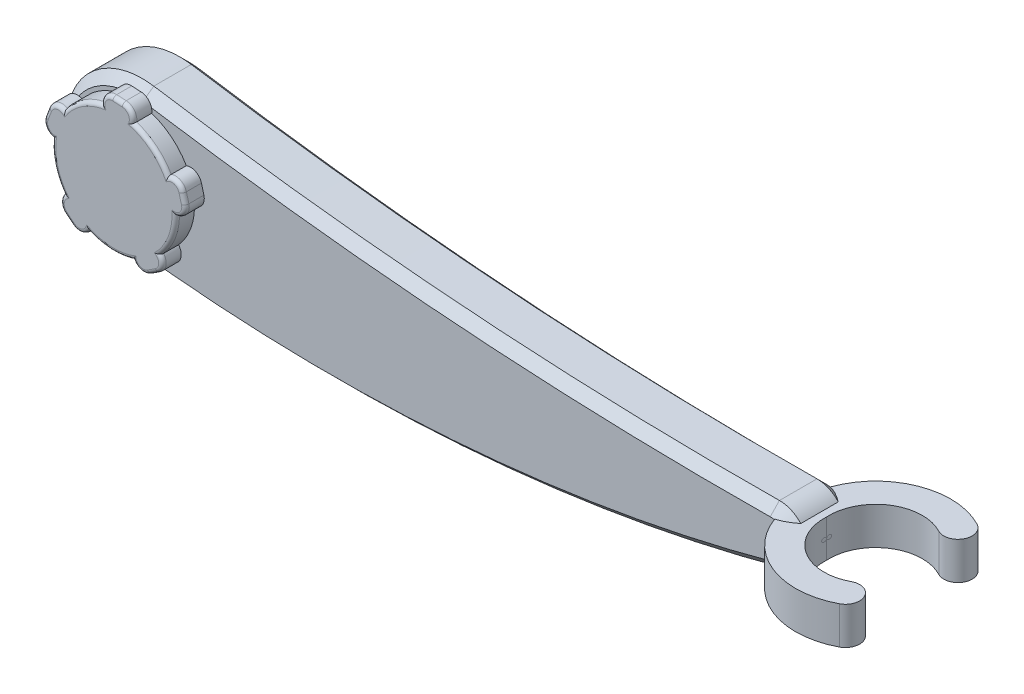
SolidWorks part; units mm, degrees
ref_plane "Front Plane" through (0, 0, 0) normal (0, 0, 1) x (1, 0, 0)
ref_plane "Top Plane" through (0, 0, 0) normal (0, 1, 0) x (1, 0, 0)
ref_plane "Right Plane" through (0, 0, 0) normal (1, 0, 0) x (0, 0, -1)
sketch "Sketch1" plane through (0, 0, 0) normal (0, 0, 1) x (1, 0, 0)
  line L0 (-61.6804, 0) -> (108.3196, 0) construction
  circle A0 centre (-61.6804, 0) radius 20
  circle A1 centre (108.3196, 0) radius 7.5
  arc A2 (-58.5521, 19.7538) -> (108.2417, 7.4996) centre (97.86, 1007.4457) ccw
  arc A3 (-64.1419, -19.8479) -> (110.304, -7.2327) centre (-8.7576, 426.7308) ccw
  dimension "D2" = 15
  dimension "D3" = 40
  dimension "D4" = 1000
  dimension "D5" = 450
  dimension "D1" = 170
extrude "Boss-Extrude1" add sketch "Sketch1" along normal mid plane 15 contours L0 A0 A3 A1 | A1 | A0 | A0 L0 A1 A2 region at (16.8751, 6.0296, 0) region at (-48.8117, -14.5633, 0) region at (20.2083, -10.4688, 0) region at (103.1396, 5.1265, 0)
chamfer "Chamfer1" distance 2.5 angle 45 8 edges at (-81.4841, 2.7953, -7.5) (23.6998, -22.0971, -7.5) (115.7472, 1.0397, -7.5) (24.5882, 10.1337, -7.5) (115.7472, 1.0397, 7.5) (23.6998, -22.0971, 7.5) (-81.4841, 2.7953, 7.5) (24.5882, 10.1337, 7.5)
sketch "Sketch2" plane through (0, 0, 7.5) normal (0, 0, 1) x (1, 0, 0)
  circle A0 centre (-61.6804, 0) radius 16.5
  dimension "D1" = 33
extrude "Boss-Extrude2" add sketch "Sketch2" along normal blind 5
sketch "Sketch3" plane through (0, 0, 12.5) normal (0, 0, 1) x (1, 0, 0)
  line L0 (-61.6804, 0) -> (-45.5901, 0)
  line L1 (-42.6923, 3.7765) -> (-43.348, 6.2235)
  line L2 (-47.7458, 8.0452) -> (-61.6804, 0)
  line L3 (-61.6804, 0) -> (-43.0201, 5) construction
  line L4 (-49.723, -10.7665) -> (-61.6804, 0)
  line L5 (-61.6804, 0) -> (-56.7082, -15.3028)
  line L6 (-52.2211, -16.8918) -> (-50.0964, -15.512)
  line L7 (-68.2249, -14.6992) -> (-61.6804, 0)
  line L8 (-61.6804, 0) -> (-74.6977, -9.4577)
  line L9 (-74.8223, -14.2161) -> (-72.8535, -15.8105)
  line L10 (-77.6826, 1.6819) -> (-61.6804, 0)
  line L11 (-61.6804, 0) -> (-74.6977, 9.4577)
  line L12 (-79.2618, 8.1057) -> (-80.1697, 5.7406)
  line L13 (-65.0258, 15.7387) -> (-61.6804, 0)
  line L14 (-61.6804, 0) -> (-56.7082, 15.3028)
  line L15 (-59.4044, 19.2257) -> (-61.9343, 19.3583)
  arc A0 (-42.6923, 3.7765) -> (-45.5901, 0) centre (-45.5901, 3) cw
  circle A1 centre (-61.6804, 0) radius 16.5
  circle A2 centre (-61.6804, 0) radius 16.5
  arc A3 (-43.348, 6.2235) -> (-47.7458, 8.0452) centre (-46.2458, 5.4471) ccw
  arc A4 (-50.0964, -15.512) -> (-49.723, -10.7665) centre (-51.7303, -12.996) ccw
  arc A5 (-52.2211, -16.8918) -> (-56.7082, -15.3028) centre (-53.855, -14.3758) cw
  arc A6 (-72.8535, -15.8105) -> (-68.2249, -14.6992) centre (-70.9656, -13.479) ccw
  arc A7 (-74.8223, -14.2161) -> (-74.6977, -9.4577) centre (-72.9344, -11.8847) cw
  arc A8 (-80.1697, 5.7406) -> (-77.6826, 1.6819) centre (-77.369, 4.6655) ccw
  arc A9 (-79.2618, 8.1057) -> (-74.6977, 9.4577) centre (-76.4611, 7.0306) cw
  arc A10 (-61.9343, 19.3583) -> (-65.0258, 15.7387) centre (-62.0913, 16.3624) ccw
  arc A11 (-59.4044, 19.2257) -> (-56.7082, 15.3028) centre (-59.5614, 16.2299) cw
  circle A12 centre (-61.6804, 0) radius 2
  point P9 (-41.6804, 0)
  point P39 (-61.6804, 0)
  circle M28 centre (-61.6804, 0) radius 16.5
  dimension "D4" = 3
  dimension "D6" = 4
  dimension "D2" = 30
  dimension "D3" = 20
  dimension "D1" = 0
  dimension "D5" = 5
extrude "Boss-Extrude3" add sketch "Sketch3" against normal blind 5 contours A11 L15 A10 M28 | A2 L3 L1 A3 | L3 A0 L1 M28 | A5 L6 A4 M28 | A7 L9 A6 M28 | A9 L12 A8 M28 region at (-45.1235, 6.4563, 12.5) region at (-44.1136, 2.6871, 12.5) region at (-52.06, -14.8141, 12.5) region at (-72.7965, -13.7273, 12.5) region at (-78.1709, 6.3301, 12.5) region at (-60.7559, 17.6395, 12.5)
fillet "Fillet1" radius 1 20 edges at (-64.2338, 18.4623, 12.5) (-60.6693, 19.292, 12.5) (-57.2111, 18.0943, 12.5) (-51.2966, 12.8229, 12.5) (-44.9107, 8.1337, 12.5) (-43.0201, 5, 12.5) (-43.0906, 1.3409, 12.5) (-46.2763, -5.9131, 12.5) (-48.7627, -13.4355, 12.5) (-51.1588, -16.2019, 12.5) (-54.6606, -17.2656, 12.5) (-62.5439, -16.4774, 12.5) (-70.4665, -16.4372, 12.5) (-73.8379, -15.0133, 12.5) (-75.9317, -12.0116, 12.5) (-77.6182, -4.2705, 12.5) (-80.0282, 3.2767, 12.5) (-79.7158, 6.9231, 12.5) (-77.508, 9.842, 12.5) (-70.6669, 13.8381, 12.5)
sketch "Sketch4" plane through (0, 0, 7.5) normal (0, 0, 1) x (1, 0, 0)
  circle A1 centre (108.3196, 0) radius 5
  dimension "D1" = 10
extrude "Cut-Extrude1" [suppressed] cut sketch "Sketch4" against normal blind 10
sketch "Sketch7" plane through (0, 0, -7.5) normal (0, 0, -1) x (-1, 0, 0)
  circle A0 centre (61.6804, 0) radius 5
  dimension "D1" = 10
extrude "Boss-Extrude4" add sketch "Sketch7" along normal blind 10
sketch "Sketch8" plane through (0, 0, 0) normal (0, 1, 0) x (1, 0, 0)
  line L0 (0, 0) -> (167.1151, 0) construction
  line L1 (108.2417, -5) -> (108.2417, 5) construction
  line L2 (115.8196, -5) -> (115.8196, 5) construction
  arc A0 (108.2417, 0) -> (137.5914, 18.3453) centre (128.2305, 0.6712) cw
  arc A1 (115.8196, 0) -> (134.0478, 11.6547) centre (128.2305, 0.6712) cw
  arc A2 (137.5914, 18.3453) -> (134.0478, 11.6547) centre (135.8196, 15) cw
  arc A3 (137.5914, -18.3453) -> (134.0478, -11.6547) centre (135.8196, -15) ccw
  arc A4 (115.8196, 0) -> (134.0478, -11.6547) centre (128.2305, -0.6712) ccw
  arc A5 (108.2417, 0) -> (137.5914, -18.3453) centre (128.2305, -0.6712) ccw
  point P14 (0, 0)
  point P16 (183.476, 14.5343)
  dimension "D1" = 15
  dimension "D3" = 20
  dimension "D2" = 20
extrude "Boss-Extrude5" add sketch "Sketch8" along normal mid plane 10
